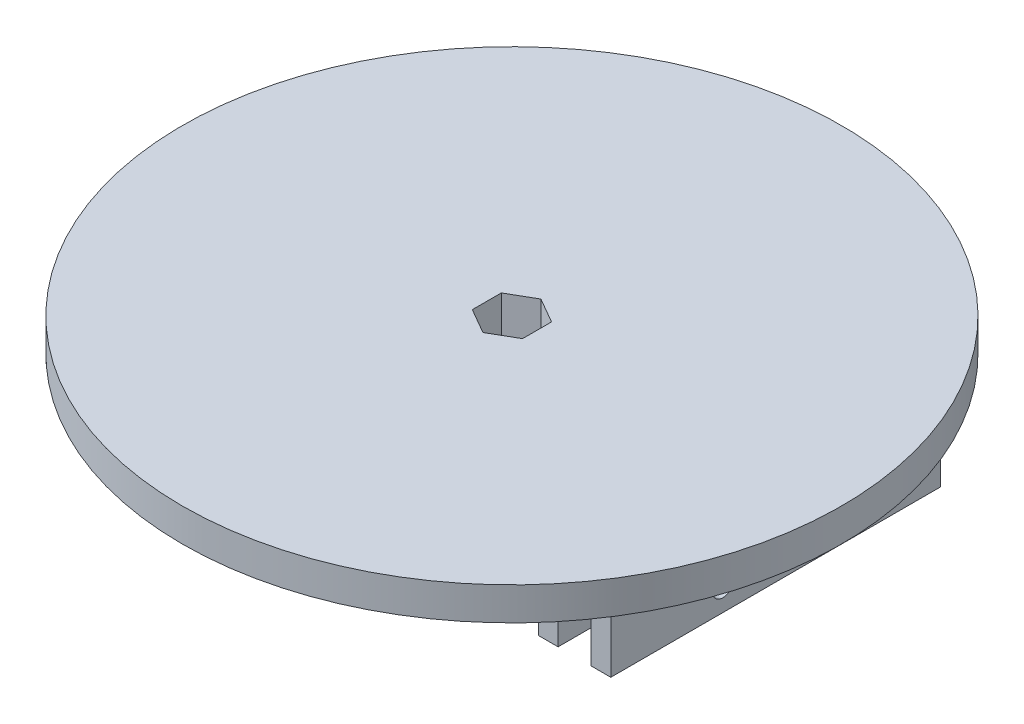
SolidWorks part; units mm, degrees
ref_plane "Front Plane" through (0, 0, 0) normal (0, 0, 1) x (1, 0, 0)
ref_plane "Top Plane" through (0, 0, 0) normal (0, 1, 0) x (1, 0, 0)
ref_plane "Right Plane" through (0, 0, 0) normal (1, 0, 0) x (0, 0, -1)
sketch "Sketch2" plane through (0, 0, 0) normal (0, 1, 0) x (1, 0, 0)
  circle A0 centre (0, 0) radius 9
extrude "Boss-Extrude1" add sketch "Sketch2" along normal blind 20
sketch "Sketch3" plane through (0, 20, 0) normal (0, 1, 0) x (1, 0, 0)
  line L0 (-3.8105, -2.2) -> (3.8105, 2.2) construction
  line L1 (0, -4.4) -> (0, 4.4) construction
  line L2 (3.8105, -2.2) -> (-3.8105, 2.2) construction
  line L15 (0, 4.4) -> (-3.8105, 2.2)
  line L16 (-3.8105, 2.2) -> (-3.8105, -2.2)
  line L17 (-3.8105, -2.2) -> (0, -4.4)
  line L18 (0, -4.4) -> (3.8105, -2.2)
  line L19 (3.8105, -2.2) -> (3.8105, 2.2)
  line L20 (3.8105, 2.2) -> (0, 4.4)
  circle A0 centre (0, 0) radius 4.4 construction
  point P4 (0, 0)
  point P5 (0, 0)
  point P6 (0, 0)
  point P9 (0, 0)
  point P10 (0, 0)
  point P11 (0, 0)
  point P14 (0, 0)
  point P15 (0, 0)
  point P17 (0, 0)
  point P20 (0, 0)
extrude "Cut-Extrude1" cut sketch "Sketch3" against normal blind 20
sketch "Sketch4" plane through (0, 20, 0) normal (0, 1, 0) x (1, 0, 0)
  circle A0 centre (0, 0) radius 50
  circle A1 centre (0, 0) radius 4.5
extrude "Boss-Extrude3" add sketch "Sketch4" against normal blind 5
ref_plane "Plane3" through (0, 0, 0) normal (0.5, 0, -0.866) x (-0.866, 0, -0.5)
sketch "Sketch11" plane through (0, 0, 0) normal (0.5, 0, -0.866) x (-0.866, 0, -0.5)
  line L2 (0, 0) -> (0, 5) construction
  circle A0 centre (0, 5) radius 1.55
extrude "Cut-Extrude2" cut sketch "Sketch11" against normal blind 9 and the other way blind 9
ref_plane "Plane4" through (0, 0, 0) normal (-0.5, 0, -0.866) x (-0.866, 0, 0.5)
sketch "Sketch15" plane through (0, 0, 0) normal (-0.5, 0, -0.866) x (-0.866, 0, 0.5)
  line L0 (0, 0) -> (0, 9) construction
  circle A0 centre (0, 9) radius 1.55
extrude "Cut-Extrude9" cut sketch "Sketch15" against normal blind 9 and the other way blind 9
sketch "Sketch16" plane through (0, 15, 0) normal (0, -1, 0) x (1, 0, 0)
  line L0 (0, 0) -> (32, 0) construction
  line L6 (0, 0) -> (-32, 0) construction
  line L12 (-32, -25) -> (-32, 25)
  line L13 (-32, 25) -> (-29, 25)
  line L14 (-29, 25) -> (-29, -25)
  line L15 (-29, -25) -> (-32, -25)
  line L16 (-32, 0) -> (-37, 0) construction
  line L17 (-37, -25) -> (-37, 25)
  line L18 (-37, 25) -> (-40, 25)
  line L19 (-40, 25) -> (-40, -25)
  line L20 (-40, -25) -> (-37, -25)
  line L21 (32, -25) -> (32, 25)
  line L22 (32, 25) -> (29, 25)
  line L23 (29, 25) -> (29, -25)
  line L24 (29, -25) -> (32, -25)
  line L25 (32, 0) -> (37, 0) construction
  line L26 (37, -25) -> (37, 25)
  line L27 (37, 25) -> (40, 25)
  line L28 (40, 25) -> (40, -25)
  line L29 (40, -25) -> (37, -25)
  point P7 (-32, 0)
  point P14 (-37, 0)
  point P19 (32, 0)
  point P25 (37, 0)
extrude "Boss-Extrude4" add sketch "Sketch16" along normal blind 10
sketch "Sketch17" plane through (-40, 0, 0) normal (-1, 0, 0) x (0, 0, 1)
  line L0 (-25, 5) -> (-25, 8.5) construction
  line L1 (-25, 5) -> (-25, 15) construction
  line L2 (-25, 8.5) -> (-8, 8.5) construction
  line L3 (-8, 8.5) -> (8, 8.5) construction
  line L4 (-16, 11.5) -> (16, 11.5) construction
  line L5 (-25, 15) -> (-25, 11.5) construction
  line L6 (-25, 11.5) -> (-16, 11.5) construction
  circle A0 centre (-16, 11.5) radius 1.55
  circle A1 centre (-8, 8.5) radius 1.55
  circle A3 centre (8, 8.5) radius 1.55
  circle A5 centre (16, 11.5) radius 1.55
extrude "Cut-Extrude10" cut sketch "Sketch17" against normal up to surface (11 mm away) up to face at (-29, 10, 0)
sketch "Sketch18" plane through (40, 0, 0) normal (1, 0, 0) x (0, 0, -1)
  line L0 (-25, 5) -> (-25, 8.5) construction
  line L1 (-25, 8.5) -> (-8, 8.5) construction
  line L2 (-8, 8.5) -> (8, 8.5) construction
  line L3 (8, 8.5) -> (-8, 8.5) construction
  line L4 (-25, 15) -> (-25, 11.5) construction
  line L5 (-25, 5) -> (-25, 15) construction
  line L6 (-25, 11.5) -> (-16, 11.5) construction
  line L7 (-16, 11.5) -> (16, 11.5) construction
  line L8 (16, 11.5) -> (-16, 11.5) construction
  circle A0 centre (-8, 8.5) radius 1.55
  circle A1 centre (8, 8.5) radius 1.55
  circle A2 centre (16, 11.5) radius 1.55
  circle A3 centre (-16, 11.5) radius 1.55
extrude "Cut-Extrude11" cut sketch "Sketch18" against normal up to surface (11 mm away) up to face at (29, 10, 0)
sketch "Sketch19" plane through (0, 0, 0) normal (-0.5, 0, -0.866) x (-0.866, 0, 0.5)
  circle A0 centre (0, 9) radius 3.5
extrude "Cut-Extrude14" cut sketch "Sketch19" against normal blind 3 from offset 9 contours A0
extrude "Cut-Extrude15" cut sketch "Sketch19<3>" along normal blind 3 from offset 9 offset against normal yes
sketch "Sketch19<3>" plane through (0, 0, 0) normal (-0.5, 0, -0.866) x (-0.866, 0, 0.5) same geometry as "Sketch19"
sketch "Sketch20" plane through (0, 0, 0) normal (0.5, 0, -0.866) x (-0.866, 0, -0.5)
  circle A0 centre (0, 5) radius 3.5
extrude "Cut-Extrude16" cut sketch "Sketch20" against normal blind 3 from offset 9
extrude "Cut-Extrude17" cut sketch "Sketch20<2>" along normal blind 3 from offset 9 offset against normal yes
sketch "Sketch20<2>" plane through (0, 0, 0) normal (0.5, 0, -0.866) x (-0.866, 0, -0.5) same geometry as "Sketch20"
